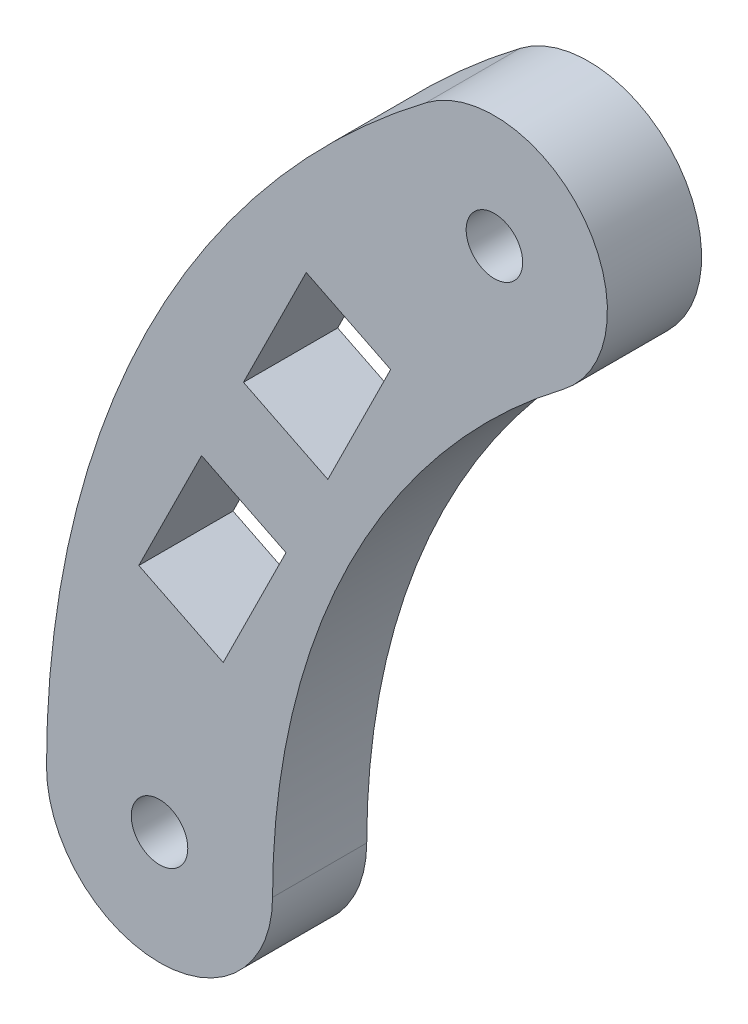
SolidWorks part; units mm, degrees
ref_plane "Plan de face" through (0, 0, 0) normal (0, 0, 1) x (1, 0, 0)
ref_plane "Plan de dessus" through (0, 0, 0) normal (0, 1, 0) x (1, 0, 0)
ref_plane "Plan de droite" through (0, 0, 0) normal (1, 0, 0) x (0, 0, -1)
sketch "Esquisse1" plane through (0, 0, 0) normal (0, 0, 1) x (1, 0, 0)
  line L0 (-27.2222, 35.8323) -> (0, 0) construction
  line L1 (0, 0) -> (-45, 0) construction
  line L2 (-46.8104, 4.6506) -> (-32.0684, 34.3641) construction
  line L3 (0, 0) -> (-40.3113, 20) construction
  line L4 (-32.7315, 27.4025) -> (-36.0649, 20.684)
  line L5 (-36.0649, 20.684) -> (-40.5439, 22.9062)
  line L6 (-40.5439, 22.9062) -> (-37.2106, 29.6247)
  line L7 (-37.2106, 29.6247) -> (-32.7315, 27.4025)
  line L8 (-46.0994, 11.7086) -> (-41.6204, 9.4864)
  line L9 (-42.7661, 18.4272) -> (-46.0994, 11.7086)
  line L10 (-38.2871, 16.2049) -> (-42.7661, 18.4272)
  line L11 (-41.6204, 9.4864) -> (-38.2871, 16.2049)
  arc A0 (-45, 0) -> (-27.2222, 35.8323) centre (0, 0) cw construction
  arc A1 (-30.8519, 40.6099) -> (-51, 0) centre (0, 0) ccw
  arc A2 (-23.5926, 31.0546) -> (-39, 0) centre (0, 0) ccw
  arc A3 (-23.5926, 31.0546) -> (-30.8519, 40.6099) centre (-27.2222, 35.8323) ccw
  arc A4 (-51, 0) -> (-39, 0) centre (-45, 0) ccw
  circle A5 centre (-27.2222, 35.8323) radius 1.5
  circle A6 centre (-45, 0) radius 1.5
  point P4 (-40.3113, 20)
  dimension "D1" = 40
  dimension "D2" = 3
  dimension "D3" = 6
  dimension "D4" = 45
  dimension "D5" = 1
  dimension "D6" = 7.5
  dimension "D7" = 5
  dimension "D8" = 2.5
extrude "Boss.-Extru.1" add sketch "Esquisse1" along normal blind 5
